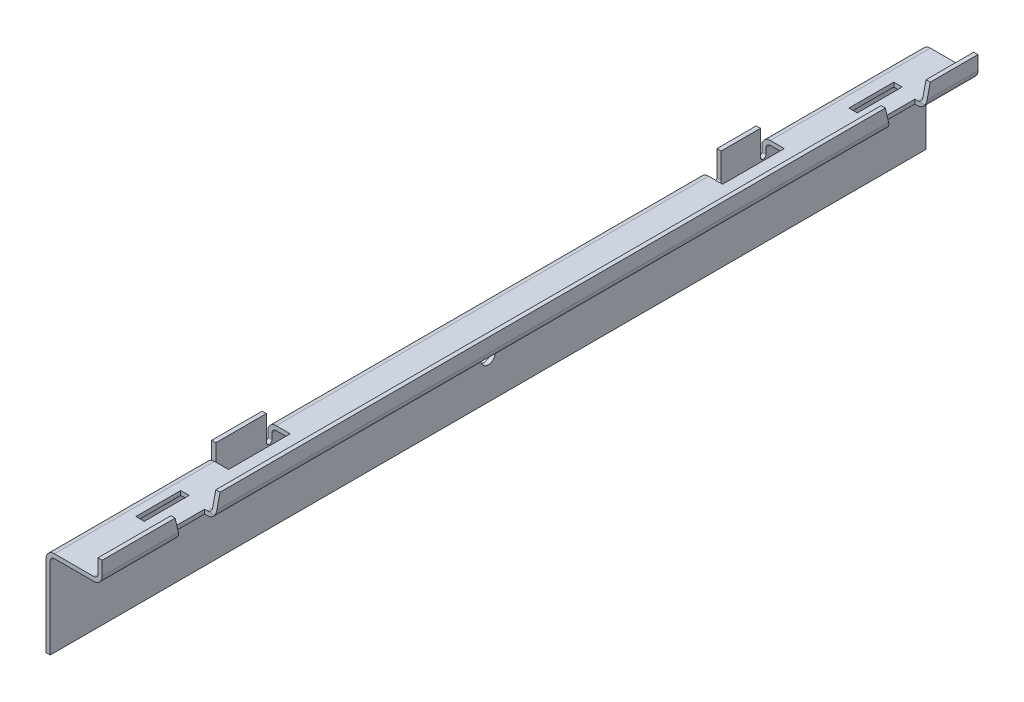
SolidWorks part; units mm, degrees
ref_plane "Front Plane" through (0, 0, 0) normal (0, 0, 1) x (1, 0, 0)
ref_plane "Top Plane" through (0, 0, 0) normal (0, 1, 0) x (1, 0, 0)
ref_plane "Right Plane" through (0, 0, 0) normal (1, 0, 0) x (0, 0, -1)
sketch "Sketch1" plane through (0, 0, 0) normal (0, 0, 1) x (1, 0, 0)
  line L0 (0, 46.0375) -> (0, 0)
  line L1 (0, 0) -> (2.3812, 0)
  line L2 (2.3812, 0) -> (2.3812, 46.0375)
  line L3 (29.3687, 53.1812) -> (29.3687, 61.1187)
  line L4 (4.7625, 50.8) -> (26.9875, 50.8)
  line L5 (26.9875, 48.4187) -> (4.7625, 48.4187)
  line L6 (31.75, 61.1187) -> (31.75, 53.1812)
  line L7 (29.3687, 61.1187) -> (31.75, 61.1187)
  arc A0 (4.7625, 50.8) -> (0, 46.0375) centre (4.7625, 46.0375) ccw
  arc A1 (26.9875, 50.8) -> (29.3687, 53.1812) centre (26.9875, 53.1812) ccw
  arc A2 (4.7625, 48.4187) -> (2.3812, 46.0375) centre (4.7625, 46.0375) ccw
  arc A3 (26.9875, 48.4187) -> (31.75, 53.1812) centre (26.9875, 53.1812) ccw
extrude "Extrude1" add sketch "Sketch1" along normal mid plane 495.3
sketch "Sketch2" plane through (0, 0, 0) normal (-1, 0, 0) x (0, 0, 1)
  line L0 (0, 0) -> (0, 61.1188) construction
  line L1 (247.65, 61.1187) -> (-247.65, 61.1187) construction
  line L2 (0, 50.8) -> (-157.1625, 50.8) construction
  line L3 (247.65, 50.8) -> (-247.65, 50.8) construction
  line L4 (-157.1625, 50.8) -> (-157.1625, 41.275)
  line L5 (-157.1625, 41.275) -> (-122.2375, 41.275)
  line L6 (-122.2375, 41.275) -> (-122.2375, 50.8)
  line L7 (-122.2375, 50.8) -> (-157.1625, 50.8)
  line L8 (0, 50.8) -> (157.1625, 50.8) construction
  line L9 (157.1625, 50.8) -> (157.1625, 41.275)
  line L10 (157.1625, 41.275) -> (122.2375, 41.275)
  line L11 (122.2375, 41.275) -> (122.2375, 50.8)
  line L12 (122.2375, 50.8) -> (157.1625, 50.8)
extrude "Cut-Extrude1" cut sketch "Sketch2" against normal blind 12.7
sketch "Sketch3" plane through (0, 41.275, 0) normal (0, 1, 0) x (1, 0, 0)
  line L0 (2.3812, 157.1625) -> (2.3812, 153.9875) construction
  line L1 (2.3812, 157.1625) -> (2.3812, 122.2375) construction
  line L2 (2.3812, 153.9875) -> (0, 153.9875)
  line L3 (0, 153.9875) -> (0, 131.7625)
  line L4 (0, 157.1625) -> (0, 122.2375) construction
  line L5 (0, 131.7625) -> (2.3812, 131.7625)
  line L6 (2.3812, 131.7625) -> (2.3812, 153.9875)
  line L7 (2.3812, -157.1625) -> (2.3812, -153.9875) construction
  line L8 (2.3812, -122.2375) -> (2.3812, -157.1625) construction
  line L9 (2.3812, -153.9875) -> (0, -153.9875)
  line L10 (0, -122.2375) -> (0, -157.1625) construction
  line L11 (0, -153.9875) -> (0, -125.4125)
  line L12 (0, -125.4125) -> (2.3812, -125.4125)
  line L13 (2.3812, -125.4125) -> (2.3812, -153.9875)
extrude "Extrude2" add sketch "Sketch3" along normal blind 15.875
fillet "Fillet1" radius 1.5875 7 edges at (1.1906, 41.275, -153.9875) (1.1906, 41.275, -131.7625) (1.1906, 41.275, -157.1625) (1.1906, 41.275, 153.9875) (1.1906, 41.275, 122.2375) (1.1906, 41.275, 157.1625) (1.1906, 41.275, 125.4125)
sketch "Sketch4" plane through (0, 50.8, 0) normal (0, 1, 0) x (1, 0, 0)
  line L0 (0, 157.1625) -> (0, 195.2625) construction
  line L1 (0, 157.1625) -> (0, 247.65) construction
  line L2 (0, 195.2625) -> (11.1125, 195.2625) construction
  line L3 (11.1125, 195.2625) -> (11.1125, 220.6625)
  line L4 (11.1125, 220.6625) -> (15.875, 220.6625)
  line L5 (15.875, 220.6625) -> (15.875, 195.2625)
  line L6 (15.875, 195.2625) -> (11.1125, 195.2625)
  line L7 (0, -157.1625) -> (0, -180.975) construction
  line L8 (0, -247.65) -> (0, -157.1625) construction
  line L9 (0, -180.975) -> (9.525, -180.975) construction
  line L10 (9.525, -180.975) -> (9.525, -206.375)
  line L11 (9.525, -206.375) -> (14.2875, -206.375)
  line L12 (14.2875, -206.375) -> (14.2875, -180.975)
  line L13 (14.2875, -180.975) -> (9.525, -180.975)
  line L14 (31.75, -247.65) -> (31.75, 247.65) construction
  dimension "D1" = 17.4625
  dimension "D2" = 15.875
extrude "Cut-Extrude2" cut sketch "Sketch4" against normal up to surface (2.3813 mm away) up to face at (11.1125, 48.4187, 0)
sketch "Sketch5" plane through (31.75, 0, 0) normal (1, 0, 0) x (0, 0, -1)
  line L0 (195.2625, 50.8) -> (195.2625, 61.1187) construction
  line L1 (-247.65, 61.1187) -> (247.65, 61.1187) construction
  line L2 (220.6625, 50.8) -> (220.6625, 61.1187) construction
  line L3 (195.2625, 61.1187) -> (220.6625, 61.1187)
  line L4 (195.2625, 50.8) -> (197.6437, 50.8) construction
  line L5 (-247.65, 50.8) -> (247.65, 50.8) construction
  line L6 (220.6625, 50.8) -> (218.2812, 50.8) construction
  line L7 (197.6437, 50.8) -> (197.6437, 48.4187)
  line L8 (-247.65, 48.4187) -> (247.65, 48.4187) construction
  line L9 (197.6437, 48.4187) -> (218.2812, 48.4187)
  line L10 (218.2812, 48.4187) -> (218.2812, 50.8)
  line L11 (220.6625, 61.1187) -> (218.2812, 50.8)
  line L12 (195.2625, 61.1187) -> (197.6437, 50.8)
  line L13 (-206.375, 50.8) -> (-206.375, 61.1187) construction
  line L14 (-180.975, 50.8) -> (-180.975, 61.1187) construction
  line L15 (-180.975, 61.1187) -> (-206.375, 61.1187)
  line L16 (-206.375, 50.8) -> (-203.9938, 50.8) construction
  line L17 (-180.975, 50.8) -> (-183.3562, 50.8) construction
  line L18 (-183.3562, 50.8) -> (-183.3562, 48.4187)
  line L19 (-183.3562, 48.4187) -> (-203.9938, 48.4187)
  line L20 (-203.9938, 48.4187) -> (-203.9938, 50.8)
  line L21 (-206.375, 61.1187) -> (-203.9938, 50.8)
  line L22 (-180.975, 61.1187) -> (-183.3562, 50.8)
extrude "Cut-Extrude3" cut sketch "Sketch5" against normal blind 6.35
sketch "Sketch6" plane through (0, 0, 0) normal (-1, 0, 0) x (0, 0, 1)
  line L0 (0, 0) -> (0, 22.225) construction
  circle A0 centre (0, 22.225) radius 3.9688
extrude "Cut-Extrude4" cut sketch "Sketch6" against normal up to surface (2.3813 mm away) up to face at (2.3812, 42.039, -0.8074)
